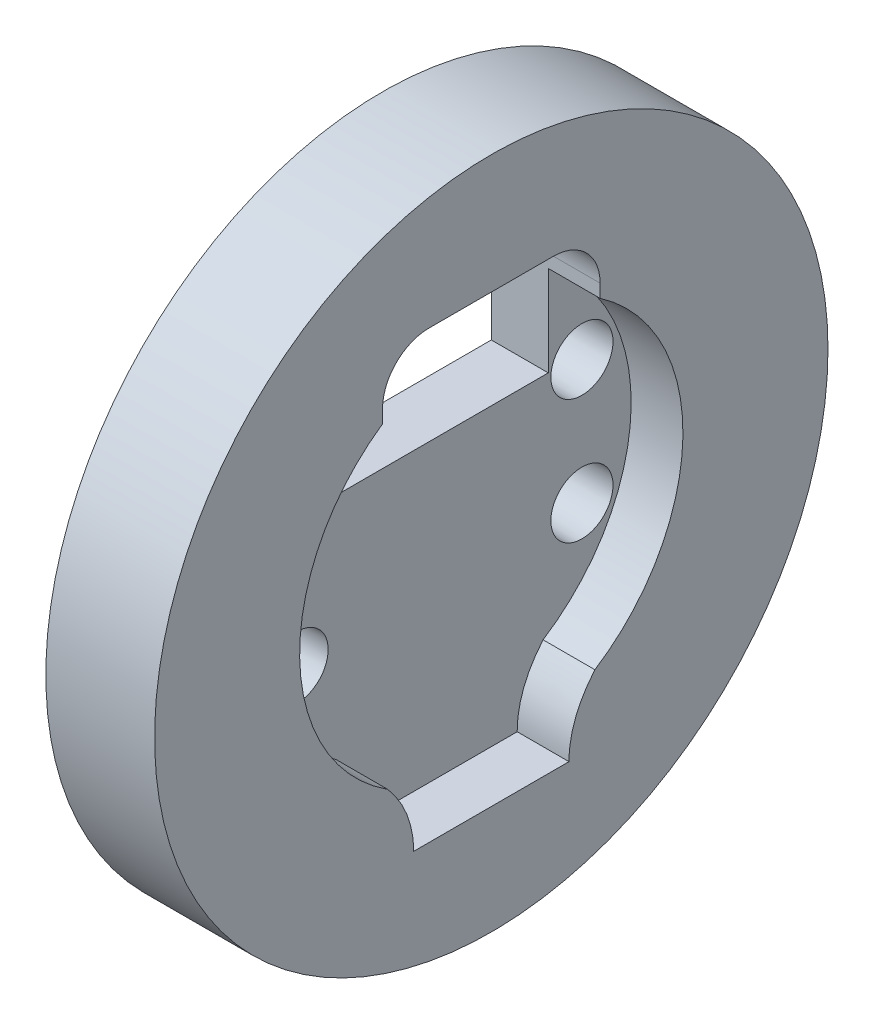
SolidWorks part; units mm, degrees
note: The reader was unsure of these and kept them because the rebuilt part matched: shared geometry of "Sketch4<3>", "Sketch5<4>".
ref_plane "Front Plane" through (0, 0, 0) normal (0, 0, 1) x (1, 0, 0)
ref_plane "Top Plane" through (0, 0, 0) normal (0, 1, 0) x (1, 0, 0)
ref_plane "Right Plane" through (0, 0, 0) normal (1, 0, 0) x (0, 0, -1)
sketch "Sketch2" plane through (0, 0, 0) normal (1, 0, 0) x (0, 0, -1)
  circle A0 centre (0, 0) radius 32.5
  dimension "D1" = 65
extrude "Boss-Extrude1" add sketch "Sketch2" against normal blind 10.5
sketch "Sketch3" plane through (0, 0, 0) normal (1, 0, 0) x (0, 0, -1)
  line L0 (-7.5, -22) -> (7.5, -22)
  line L1 (-10, -15.5644) -> (-7.5, -18.5) construction
  line L2 (-7.5, -18.5) -> (-7.5, -22) construction
  line L3 (0, -22) -> (0, -18.5)
  line L6 (10, -15.5644) -> (7.5, -18.5) construction
  line L7 (7.5, -18.5) -> (7.5, -22) construction
  circle A2 centre (0, 0) radius 18.5
  spline S0 degree 2 poles (-10, -15.5644) (-7.5, -18.5) (-7.5, -22) knots 0 0 0 1 1 1
  spline S2 degree 2 poles (10, -15.5644) (7.5, -18.5) (7.5, -22) knots 0 0 0 1 1 1
  dimension "D1" = 37
  dimension "D6" = 20
  dimension "D2" = 3.5
  dimension "D3" = 3.5
  dimension "D4" = 7.5
  dimension "D5" = 15
extrude "Cut-Extrude1" cut sketch "Sketch3" against normal offset from surface (5 mm away) 5.5
sketch "Sketch4" plane through (-5, 0, 0) normal (1, 0, 0) x (0, 0, -1)
  line L0 (13.7477, 6) -> (-13.7477, -6)
  line L1 (-6, 21) -> (10.5, 21)
  line L2 (-10.5, 16.5) -> (-10.5, 6.5)
  line L3 (-10.5, 6.5) -> (10.5, 6.5)
  line L4 (10.5, 21) -> (10.5, 6.5)
  line L5 (-10.5, 21) -> (10.5, 6.5) construction
  line L6 (-10.5, 6.5) -> (10.5, 21) construction
  line L7 (-13.7477, 6) -> (13.7477, -6)
  line L8 (13.7477, 6) -> (13.7477, -6)
  line L9 (-13.7477, 6) -> (-13.7477, -6)
  line L10 (-13.7477, 6) -> (13.7477, 6)
  line L11 (-13.7477, -6) -> (13.7477, -6)
  line L12 (0, 21) -> (0, 6.5)
  line L13 (-10.5, 16.5) -> (-10.5, 21)
  line L14 (-10.5, 21) -> (-6, 21)
  arc A1 (-6, 21) -> (-10.5, 16.5) centre (-6, 16.5) ccw
  circle A2 centre (-13.7477, 6) radius 3
  circle A3 centre (13.7477, 6) radius 3
  circle A4 centre (13.7477, -6) radius 3
  circle A5 centre (-13.7477, -6) radius 3
  arc A6 (6, 21) -> (10.5, 16.5) centre (6, 16.5) cw
  point P0 (0, 13.75)
  point P18 (0, 0)
  arc M5 (10, -15.5644) -> (-10, -15.5644) centre (0, 0) ccw
  dimension "D3" = 6.5
  dimension "D4" = 6
  dimension "D7" = 4.5
  dimension "D1" = 14.5
  dimension "D2" = 21
  dimension "D5" = 30
  dimension "D6" = 12
extrude "Cut-Extrude2" cut sketch "Sketch4" against normal through all and the other way blind 10 contours L4 L2 L3 M5 | L12 L2 L3 M5 | L1 A1 L2 L12 M5 | A6 L1 L12 L4 M5
extrude "Cut-Extrude4" cut sketch "Sketch4<3>" against normal up to surface (5.5 mm away) draft 1 contours L10 A2 L9 | L9 A2 L7 | L7 A2 L10 | L9 A5 L11 | L0 A5 L9 | L11 A5 L0 | L8 A3 L10 | L10 A3 L0 | L0 A3 L8 | L11 A4 L8 | L8 A4 L7 | L7 A4 L11
sketch "Sketch4<3>" plane through (-5, 0, 0) normal (1, 0, 0) x (0, 0, -1) same geometry as "Sketch4"
sketch "Sketch5" plane through (-10.5, 0, 0) normal (-1, 0, 0) x (0, 0, 1)
  line L0 (-1.5, 0) -> (-1.5, -1)
  line L1 (-1.5, -1) -> (1.5, -1)
  line L2 (1.5, -1) -> (1.5, 0)
  line L3 (1.5, -1) -> (5, -1)
  line L4 (5, -1) -> (5, 1.5)
  line L5 (5, 1.5) -> (0, 1.5)
  line L6 (-1, -5) -> (1.5, -5)
  line L7 (-1, -1.5) -> (-1, -5)
  line L8 (1.5, -5) -> (1.5, 0)
  line L9 (-5, 1) -> (-5, -1.5)
  line L10 (-1.5, 1) -> (-5, 1)
  line L11 (-5, -1.5) -> (0, -1.5)
  line L12 (1, 5) -> (-1.5, 5)
  line L13 (1, 1.5) -> (1, 5)
  line L14 (-1.5, 5) -> (-1.5, 0)
  line L15 (0, -1.5) -> (0, -1)
  line L16 (0, -1.5) -> (1.5, -1.5)
  arc A1 (1.5, 0) -> (-1.5, 0) centre (0, 0) ccw
  point P24 (0, 0)
  point P25 (0, 0)
  dimension "D1" = 3
  dimension "D2" = 1
  dimension "D3" = 5
  dimension "D4" = 4
extrude "Extrude-Thin1" add sketch "Sketch5" along normal blind 4 and the other way up to surface (5.5 mm away) separate body thin contours A1 L0 L1 L2
extrude "Boss-Extrude8" add sketch "Sketch5<4>" along normal blind 4 and the other way up to surface (5.5 mm away) separate body
sketch "Sketch5<4>" plane through (-10.5, 0, 0) normal (-1, 0, 0) x (0, 0, 1) same geometry as "Sketch5"
sketch "Sketch10" plane through (-10.5, 0, 0) normal (-1, 0, 0) x (0, 0, 1)
  line L0 (1.5, -1) -> (1.5, 0) construction
  line L1 (-1.5, 0) -> (-1.5, -1) construction
  line L2 (-1.5, -1) -> (1.5, -1) construction
  line L3 (1.5, -1) -> (1.5, 0)
  line L4 (-1.5, 0) -> (-1.5, -1)
  line L5 (-1.5, -1) -> (1.5, -1)
  arc A0 (1.5, 0) -> (-1.5, 0) centre (0, 0) ccw construction
  arc A1 (1.5, 0) -> (-1.5, 0) centre (0, 0) ccw
extrude "Cut-Extrude5" cut sketch "Sketch10" against normal offset from surface (3.5 mm away) 2 up to face at (-5, -6, 10.7477)
sketch "Sketch8" plane through (-5, 0, 0) normal (-1, 0, 0) x (0, 0, 1)
  point P0 (0, 0)
sketch "Sketch9" plane through (-5, 0, 0) normal (1, 0, 0) x (0, 0, -1)
  point P0 (0, 0)
